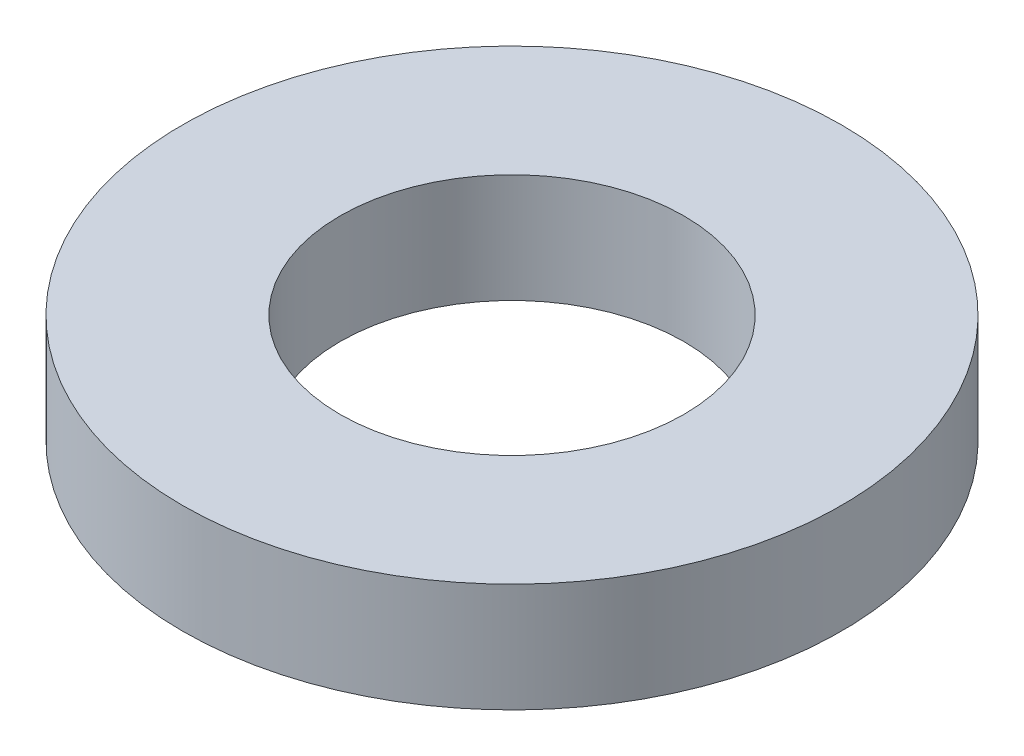
SolidWorks part; units mm, degrees
ref_plane "Front Plane" through (0, 0, 0) normal (0, 0, 1) x (1, 0, 0)
ref_plane "Top Plane" through (0, 0, 0) normal (0, 1, 0) x (1, 0, 0)
ref_plane "Right Plane" through (0, 0, 0) normal (1, 0, 0) x (0, 0, -1)
sketch "Sketch1" plane through (0, 0, 0) normal (0, 1, 0) x (1, 0, 0)
  circle A0 centre (0, 0) radius 57.5
  dimension "FLANGE_OD" = 115
extrude "Boss-Extrude1" add sketch "Sketch1" along normal blind 19
sketch "Sketch2" plane through (0, 0, 0) normal (0, 1, 0) x (1, 0, 0)
  circle A0 centre (0, 0) radius 30
  dimension "BORE_D" = 60
extrude "Cut-Extrude1" cut sketch "Sketch2" along normal through all
sketch "Sketch3" plane through (0, 19, 0) normal (0, 1, 0) x (1, 0, 0)
  circle A0 centre (0, 0) radius 17.9244 construction
  circle A1 centre (-17.9244, 0) radius 3.9866
  dimension "BOLT_D" = 7.9731
  dimension "BOLT_PCD" = 35.8487
extrude "Cut-Extrude2" cut sketch "Sketch3" against normal blind 11.7855 rebuild error yes
pattern_circular "CirPattern1" count 3 over 360 rebuild error yes
